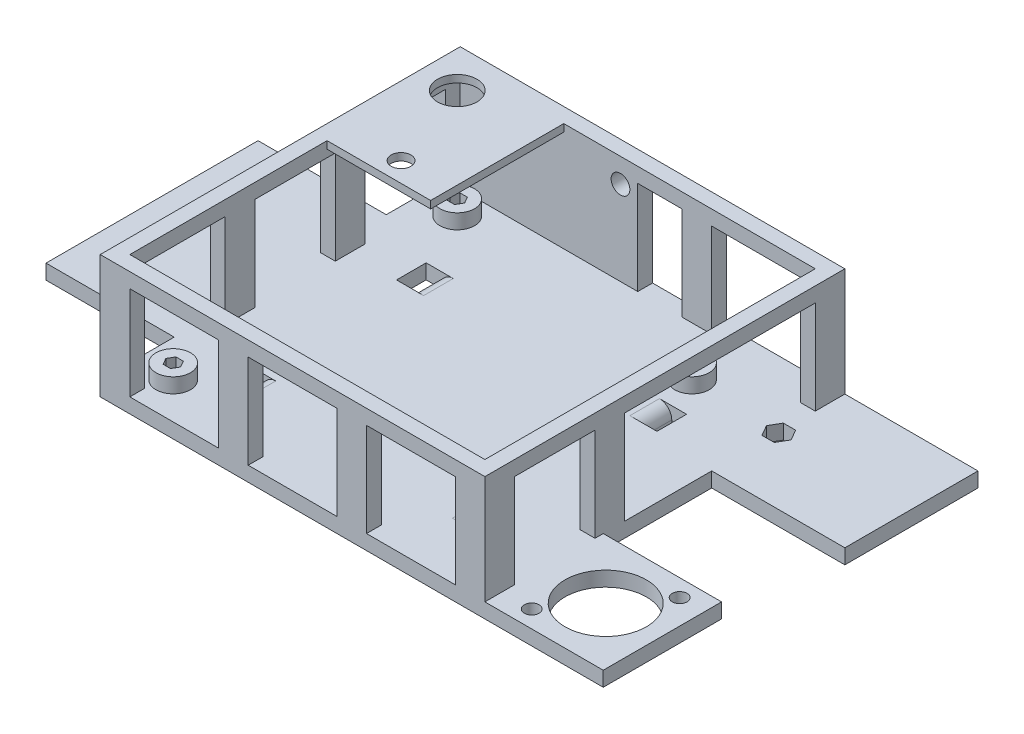
SolidWorks part; units mm, degrees
ref_plane "Front Plane" through (0, 0, 0) normal (0, 0, 1) x (1, 0, 0)
ref_plane "Top Plane" through (0, 0, 0) normal (0, 1, 0) x (1, 0, 0)
ref_plane "Right Plane" through (0, 0, 0) normal (1, 0, 0) x (0, 0, -1)
sketch "Sketch1" plane through (0, 0, 0) normal (0, 1, 0) x (1, 0, 0)
  line L0 (100, 24) -> (102, 24)
  line L1 (0, 0) -> (78, 0)
  line L2 (0, 0) -> (0, 15)
  line L3 (0, 73) -> (78, 73)
  line L4 (78, 24) -> (78, 46)
  line L5 (78, 73) -> (105, 73)
  line L7 (78, 46) -> (105, 46)
  line L8 (105, 73) -> (105, 46)
  line L13 (78, 0) -> (100, 0)
  line L15 (78, 24) -> (100, 24)
  line L17 (102, 24) -> (102, 0)
  line L18 (102, 0) -> (100, 0)
  line L19 (0, 73) -> (0, 58)
  line L21 (0, 58) -> (-26, 58)
  line L23 (0, 15) -> (-26, 15)
  line L24 (-26, 58) -> (-26, 15)
  dimension "D1" = 78
  dimension "D2" = 73
  dimension "D3" = 27
  dimension "D4" = 22
  dimension "D5" = 26
  dimension "D6" = 43
  dimension "D7" = 24
  dimension "D8" = 2
  dimension "D9" = 15
extrude "Boss-Extrude1" add sketch "Sketch1" along normal blind 3
sketch "Sketch2" plane through (0, 3, 0) normal (0, 1, 0) x (1, 0, 0)
  line L0 (105, 73) -> (0, 73) construction
  line L1 (0, 0) -> (3, 0)
  line L2 (0, 0) -> (0, 6)
  line L3 (0, 6) -> (3, 6)
  line L4 (3, 3) -> (3, 6)
  line L5 (78, 0) -> (75, 0)
  line L6 (78, 0) -> (78, 6)
  line L7 (78, 6) -> (75, 6)
  line L8 (75, 3) -> (75, 6)
  line L9 (0, 28.3333) -> (3, 28.3333)
  line L10 (0, 28.3333) -> (0, 22.3333)
  line L11 (0, 22.3333) -> (3, 22.3333)
  line L12 (3, 28.3333) -> (3, 22.3333)
  line L13 (0, 44.6663) -> (3, 44.6663)
  line L14 (0, 44.6663) -> (0, 50.6663)
  line L15 (0, 50.6663) -> (3, 50.6663)
  line L16 (3, 44.6663) -> (3, 50.6663)
  line L17 (0, 73) -> (3, 73)
  line L18 (0, 73) -> (0, 67)
  line L19 (0, 67) -> (3, 67)
  line L20 (3, 70) -> (3, 67)
  line L21 (24, 0) -> (30, 0)
  line L22 (24, 0) -> (24, 3)
  line L23 (24, 3) -> (30, 3)
  line L24 (30, 0) -> (30, 3)
  line L25 (48, 0) -> (54, 0)
  line L26 (48, 0) -> (48, 3)
  line L27 (48, 3) -> (54, 3)
  line L28 (54, 0) -> (54, 3)
  line L29 (0, 0) -> (102, 0) construction
  line L30 (0, 15) -> (0, 0) construction
  line L36 (78, 24) -> (78, 46) construction
  line L37 (78, 22.333) -> (75, 22.333)
  line L38 (78, 22.333) -> (78, 28.333)
  line L39 (78, 28.333) -> (75, 28.333)
  line L40 (75, 22.333) -> (75, 28.333)
  line L41 (105, 46) -> (105, 73) construction
  line L42 (72, 73) -> (78, 73)
  line L43 (72, 73) -> (72, 70)
  line L44 (72, 70) -> (75, 70)
  line L45 (78, 73) -> (78, 70)
  line L46 (3, 0) -> (6, 0)
  line L47 (36, 73) -> (39, 73)
  line L49 (36, 70) -> (39, 70)
  line L50 (39, 73) -> (39, 70)
  line L51 (48, 73) -> (54, 73)
  line L52 (48, 73) -> (48, 70)
  line L53 (48, 70) -> (54, 70)
  line L54 (54, 73) -> (54, 70)
  line L55 (6, 0) -> (6, 3)
  line L56 (6, 3) -> (3, 3)
  line L57 (72, 3) -> (72, 0)
  line L58 (72, 3) -> (75, 3)
  line L60 (72, 0) -> (75, 0)
  line L61 (3, 73) -> (6, 73)
  line L63 (17, 70) -> (3, 70)
  line L64 (17, 70) -> (36, 70)
  line L65 (6, 73) -> (36, 73)
  line L66 (78, 70) -> (78, 67)
  line L67 (78, 67) -> (75, 67)
  line L68 (75, 67) -> (75, 70)
  dimension "D1" = 3
  dimension "D2" = 6
  dimension "D4" = 6
  dimension "D5" = 6
  dimension "D6" = 6
  dimension "D7" = 3
  dimension "D8" = 16.3333
  dimension "D9" = 6
  dimension "D10" = 18
  dimension "D11" = 18
  dimension "D12" = 0
  dimension "D13" = 3
  dimension "D14" = 3
  dimension "D15" = 0
  dimension "D16" = 3
  dimension "D17" = 0
  dimension "D18" = 6
  dimension "D19" = 3
  dimension "D20" = 6
  dimension "D21" = 3
  dimension "D22" = 6
  dimension "D23" = 3
  dimension "D24" = 27
  dimension "D25" = 3
  dimension "D26" = 3
  dimension "D27" = 3
  dimension "D28" = 3
  dimension "D29" = 6
  dimension "D30" = 18
  dimension "D31" = 3
  dimension "D32" = 3
  dimension "D33" = 16.333
  dimension "D34" = 6
  dimension "D35" = 16.333
  dimension "D36" = 9
extrude "Boss-Extrude2" add sketch "Sketch2" along normal blind 19
sketch "Sketch3" plane through (0, 22, 0) normal (0, 1, 0) x (1, 0, 0)
  line L0 (0, 73) -> (0, 0)
  line L1 (0, 0) -> (78, 0)
  line L2 (78, 0) -> (78, 73)
  line L3 (78, 73) -> (72, 73) construction
  line L4 (78, 67) -> (78, 73) construction
  line L5 (78, 73) -> (0, 73)
  line L12 (3, 70) -> (75, 70)
  line L13 (75, 70) -> (75, 3)
  line L14 (75, 3) -> (3, 3)
  line L15 (3, 3) -> (3, 70)
extrude "Boss-Extrude3" add sketch "Sketch3" along normal blind 3
sketch "Sketch4" plane through (0, 3, 0) normal (0, 1, 0) x (1, 0, 0)
  line L0 (3, 3) -> (75, 3) construction
  line L1 (75, 3) -> (75, 70) construction
  line L2 (75, 70) -> (3, 70) construction
  line L4 (3, 70) -> (3, 3) construction
  line L5 (8.9, 65) -> (8.15, 66.299)
  line L6 (8.15, 66.299) -> (6.65, 66.299)
  line L7 (6.65, 66.299) -> (5.9, 65)
  line L8 (5.9, 65) -> (6.65, 63.701)
  line L9 (6.65, 63.701) -> (8.15, 63.701)
  line L10 (8.15, 63.701) -> (8.9, 65)
  line L11 (8.9, 7.4) -> (8.15, 8.699)
  line L12 (8.15, 8.699) -> (6.65, 8.699)
  line L13 (6.65, 8.699) -> (5.9, 7.4)
  line L14 (5.9, 7.4) -> (6.65, 6.101)
  line L15 (6.65, 6.101) -> (8.15, 6.101)
  line L16 (8.15, 6.101) -> (8.9, 7.4)
  line L17 (68.9, 7.4) -> (69.65, 6.101)
  line L18 (69.65, 6.101) -> (71.15, 6.101)
  line L19 (71.15, 6.101) -> (71.9, 7.4)
  line L20 (71.9, 7.4) -> (71.15, 8.699)
  line L21 (71.15, 8.699) -> (69.65, 8.699)
  line L22 (69.65, 8.699) -> (68.9, 7.4)
  circle A0 centre (7.4, 65) radius 3.5
  circle A1 centre (7.4, 7.4) radius 3.5
  circle A3 centre (70.4, 7.4) radius 3.5
  circle A7 centre (60, 60) radius 3.5
  circle A8 centre (7.4, 65) radius 1.299 construction
  circle A9 centre (7.4, 7.4) radius 1.299 construction
  circle A10 centre (70.4, 7.4) radius 1.299 construction
  dimension "D1" = 7
  dimension "D2" = 57.6
  dimension "D3" = 63
  dimension "D6" = 7
  dimension "D7" = 7
  dimension "D8" = 15
  dimension "D4" = 4.4
  dimension "D5" = 4.4
  dimension "D9" = 10
  dimension "D10" = 4.4
extrude "Boss-Extrude4" add sketch "Sketch4" along normal blind 3
extrude "Cut-Extrude1" cut sketch "Sketch4<2>" against normal through all contours L9 L10 L5 L6 L7 L8 | L15 L16 L11 L12 L13 L14 | L19 L20 L21 L22 L17 L18 region at (7.4, 3, -65) region at (7.4, 3, -7.4)
sketch "Sketch4<2>" plane through (0, 3, 0) normal (0, 1, 0) x (1, 0, 0) same geometry as "Sketch4"
sketch "Sketch5" plane through (0, 3, 0) normal (0, 1, 0) x (1, 0, 0)
  line L0 (105, 73) -> (78, 73) construction
  line L2 (80.6018, 59.5) -> (79.3518, 61.6651)
  line L3 (79.3518, 61.6651) -> (76.8518, 61.6651)
  line L4 (76.8518, 61.6651) -> (75.6018, 59.5)
  line L5 (75.6018, 59.5) -> (76.8518, 57.3349)
  line L6 (76.8518, 57.3349) -> (79.3518, 57.3349)
  line L7 (79.3518, 57.3349) -> (80.6018, 59.5)
  circle A1 centre (78.1018, 59.5) radius 2.1651 construction
  dimension "D1" = 13.5
extrude "Cut-Extrude2" cut sketch "Sketch5" against normal blind 3
sketch "Sketch7" plane through (0, 0, -73) normal (0, 0, -1) x (-1, 0, 0)
  line L0 (-39, 22) -> (-39, 3) construction
  line L1 (-78, 25) -> (0, 25) construction
  circle A0 centre (-35.5, 20.1) radius 1.9
  dimension "D1" = 3.8
  dimension "D2" = 3.5
  dimension "D3" = 4.9
extrude "Cut-Extrude3" cut sketch "Sketch7" against normal blind 3
sketch "Sketch8" plane through (0, 25, 0) normal (0, 1, 0) x (1, 0, 0)
  line L1 (3, 70) -> (24, 70)
  line L2 (3, 70) -> (3, 43)
  line L3 (3, 43) -> (24, 43)
  line L4 (24, 70) -> (24, 43)
  circle A0 centre (14, 47) radius 2
  circle A1 centre (7.4, 65) radius 4
  point P7 (0, 0)
  dimension "D3" = 4
  dimension "D1" = 21
  dimension "D2" = 27
  dimension "D4" = 11
  dimension "D5" = 23
extrude "Boss-Extrude5" add sketch "Sketch8" against normal blind 1.5
sketch "Sketch9" plane through (0, 3, 0) normal (0, 1, 0) x (1, 0, 0)
  line L3 (78, 0) -> (102, 0) construction
  line L4 (79.5, 23) -> (99.5, 23) construction
  line L5 (79.5, 23) -> (79.5, 1) construction
  line L6 (79.5, 1) -> (99.5, 1) construction
  line L7 (99.5, 23) -> (99.5, 1) construction
  line L8 (97, 20.5) -> (84, 3.5) construction
  circle A0 centre (97, 20.5) radius 1.5
  circle A1 centre (84, 3.5) radius 1.5
  circle A3 centre (90.5, 12) radius 8.25
  dimension "D1" = 3
  dimension "D2" = 3
  dimension "D6" = 4.5
  dimension "D7" = 20
  dimension "D3" = 2.5
  dimension "D10" = 16.5
  dimension "D4" = 2.5
  dimension "D5" = 2.5
  dimension "D8" = 22
  dimension "D9" = 1
extrude "Cut-Extrude4" cut sketch "Sketch9" against normal blind 3
sketch "Sketch10" plane through (0, 3, 0) normal (0, 1, 0) x (1, 0, 0)
  line L0 (62.5, 17.4) -> (65.5, 17.4)
  line L1 (62.5, 53.4) -> (65.5, 53.4)
  line L2 (62.5, 53.4) -> (62.5, 47.4)
  line L3 (62.5, 47.4) -> (65.5, 47.4)
  line L4 (65.5, 53.4) -> (65.5, 47.4)
  line L5 (62.5, 17.4) -> (62.5, 11.4)
  line L6 (62.5, 11.4) -> (65.5, 11.4)
  line L7 (65.5, 17.4) -> (65.5, 11.4)
  line L8 (12.5, 17.5842) -> (15.5, 17.5842)
  line L9 (12.5, 53.5842) -> (15.5, 53.5842)
  line L10 (12.5, 53.5842) -> (12.5, 47.5842)
  line L11 (12.5, 47.5842) -> (15.5, 47.5842)
  line L12 (15.5, 53.5842) -> (15.5, 47.5842)
  line L13 (12.5, 17.5842) -> (12.5, 11.5842)
  line L14 (12.5, 11.5842) -> (15.5, 11.5842)
  line L15 (15.5, 17.5842) -> (15.5, 11.5842)
  line L16 (3, 43) -> (3, 3) construction
  dimension "D1" = 3
  dimension "D2" = 6
  dimension "D4" = 30
  dimension "D5" = 47
  dimension "D6" = 47
  dimension "D7" = 9.5
  dimension "D8" = 9.5
extrude "Cut-Extrude5" cut sketch "Sketch10" against normal blind 3
fillet "Fillet1" radius 2.5 4 edges at (15.5, 3, -50.5842) (62.5, 3, -50.4) (62.5, 3, -14.4) (15.5, 3, -14.5842)
